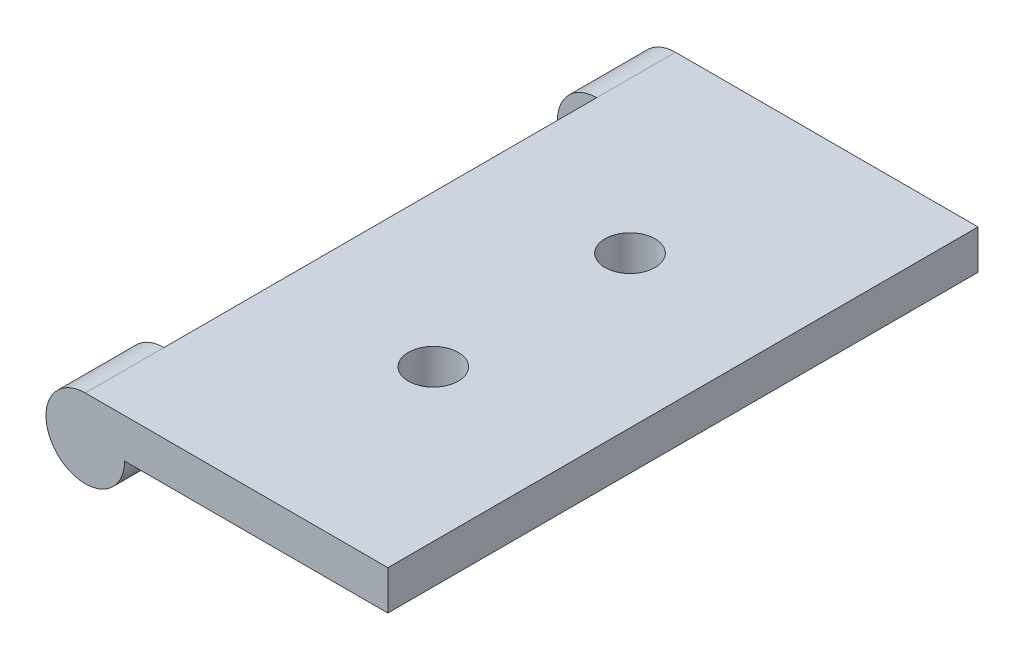
SolidWorks part; units mm, degrees
ref_plane "Front Plane" through (0, 0, 0) normal (0, 0, 1) x (1, 0, 0)
ref_plane "Top Plane" through (0, 0, 0) normal (0, 1, 0) x (1, 0, 0)
ref_plane "Right Plane" through (0, 0, 0) normal (1, 0, 0) x (0, 0, -1)
sketch "Sketch1" plane through (0, 0, 0) normal (0, 0, 1) x (1, 0, 0)
  line L3 (21.825, 0) -> (28.175, 0)
  line L4 (-98.5566, -165.7051) -> (0, 5)
  line L5 (0, 5) -> (270, 5)
  line L7 (0, 0) -> (270, 0)
  line L8 (44.2265, 0) -> (5.7735, 0)
  line L9 (5.7735, 0) -> (5.7735, -5)
  line L10 (5.7735, -5) -> (44.2265, -5)
  line L11 (44.2265, -5) -> (44.2265, 0)
  line L12 (2.8868, 0) -> (-94.2265, -168.2051)
  line L13 (-98.5566, -165.7051) -> (-94.2265, -168.2051)
  line L14 (25, 0) -> (25, -5)
  circle A0 centre (5.7735, -5) radius 5
  circle A1 centre (5.7735, -5) radius 2.5
  point P13 (25, -5)
  point P14 (25, 0)
  point P19 (5.7735, 0)
  dimension "D4" = 10
  dimension "D5" = 5
  dimension "D1" = 120
  dimension "D2" = 5
  dimension "D3" = 5
extrude "Boss-Extrude1" add sketch "Sketch1" against normal blind 75 contours L10 L11 L8 L9
extrude "Boss-Extrude2" add sketch "Sketch1<4>" against normal blind 10 contours A1 L9 A0 L10 | L9 A1 L10 region at (5.6321, -1.25, 0) region at (5.4198, -5.3537, 0)
sketch "Sketch1<4>" plane through (0, 0, 0) normal (0, 0, 1) x (1, 0, 0) same geometry as "Sketch1"
extrude "Boss-Extrude4" add sketch "Sketch1<11>" against normal blind 75 contours L9 A1 L10 region at (5.4198, -5.3537, 0)
sketch "Sketch1<11>" plane through (0, 0, 0) normal (0, 0, 1) x (1, 0, 0) same geometry as "Sketch1"
extrude "Boss-Extrude5" add sketch "Sketch1<12>" against normal blind 10 from offset 65 contours A1 L9 A0 L10 region at (5.6321, -1.25, 0) offset against normal yes
sketch "Sketch1<12>" plane through (0, 0, 0) normal (0, 0, 1) x (1, 0, 0) same geometry as "Sketch1"
extrude "Cut-Extrude7" cut sketch "Sketch1<13>" against normal blind 55 from offset 10 contours A1 L10 A0 L9 region at (8.2492, -2.5243, 0) offset against normal yes
sketch "Sketch1<13>" plane through (0, 0, 0) normal (0, 0, 1) x (1, 0, 0) same geometry as "Sketch1"
sketch "Sketch5" plane through (0, -5, 0) normal (0, -1, 0) x (1, 0, 0)
  circle A0 centre (25, -25) radius 3.175 construction
  circle A1 centre (25, -50) radius 3.175 construction
  circle A2 centre (25, -25) radius 3.175
  circle A3 centre (25, -50) radius 3.175
extrude "Cut-Extrude8" cut sketch "Sketch5" against normal blind 55
